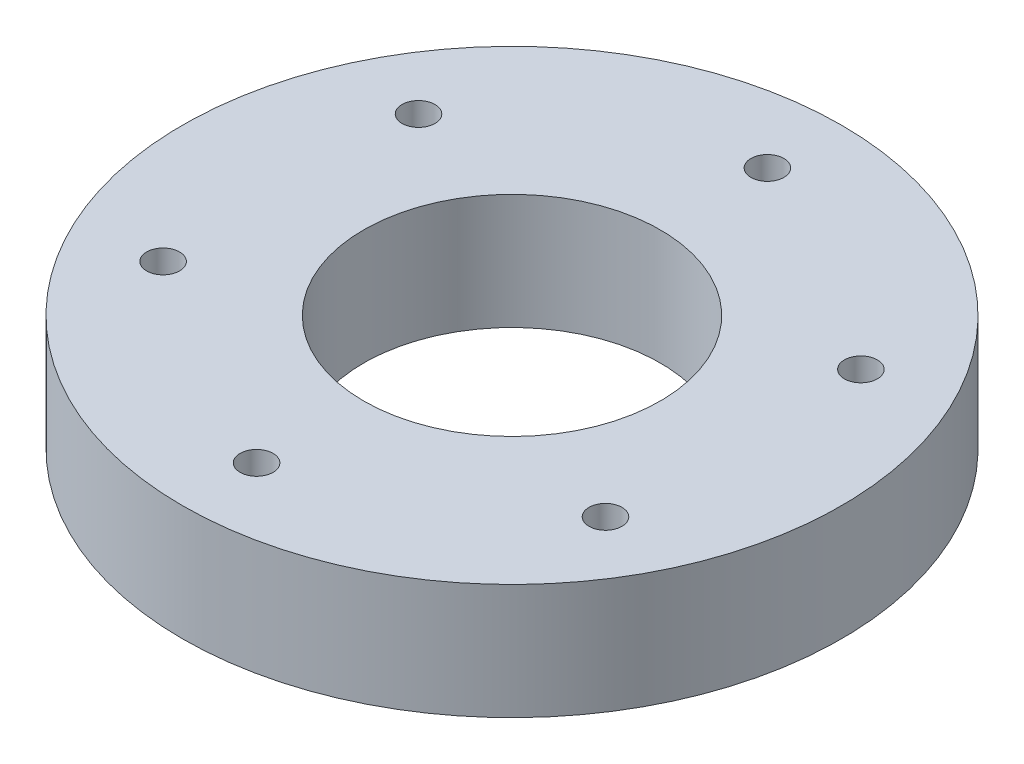
SolidWorks part; units mm, degrees
ref_plane "Front Plane" through (0, 0, 0) normal (0, 0, 1) x (1, 0, 0)
ref_plane "Top Plane" through (0, 0, 0) normal (0, 1, 0) x (1, 0, 0)
ref_plane "Right Plane" through (0, 0, 0) normal (1, 0, 0) x (0, 0, -1)
sketch "Sketch1" plane through (0, 0, 0) normal (0, 1, 0) x (1, 0, 0)
  circle A0 centre (0, 0) radius 20
  circle A1 centre (0, 0) radius 9
  circle A2 centre (0, 0) radius 15.5 construction
  circle A3 centre (0, 15.5) radius 1
  circle A4 centre (13.4234, 7.75) radius 1
  circle A5 centre (13.4234, -7.75) radius 1
  circle A6 centre (0, -15.5) radius 1
  circle A7 centre (-13.4234, -7.75) radius 1
  circle A8 centre (-13.4234, 7.75) radius 1
  point P19 (0, 0)
  dimension "D1" = 40
  dimension "D2" = 18
  dimension "D3" = 31
  dimension "D4" = 2
  dimension "D5" = 6
extrude "Boss-Extrude1" add sketch "Sketch1" along normal blind 7
